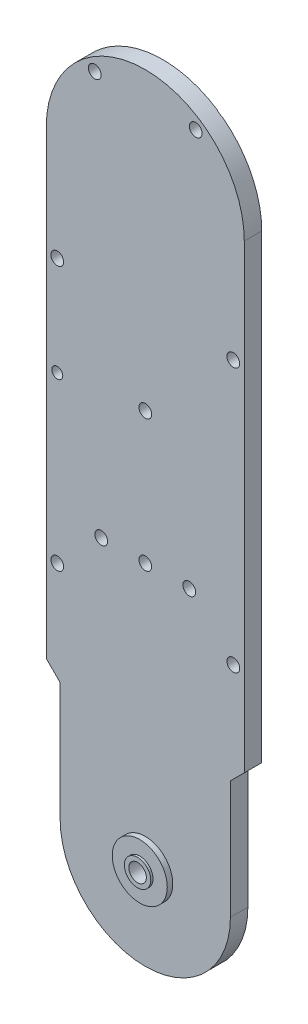
SolidWorks part; units mm, degrees
material "6061 Alloy"
ref_plane "Front Plane" through (0, 0, 0) normal (0, 0, 1) x (1, 0, 0)
ref_plane "Top Plane" through (0, 0, 0) normal (0, 1, 0) x (1, 0, 0)
ref_plane "Right Plane" through (0, 0, 0) normal (1, 0, 0) x (0, 0, -1)
sketch "Sketch1" plane through (0, 0, 0) normal (0, 0, 1) x (1, 0, 0)
  line L0 (-45, 0) -> (-45, -65.8631)
  line L1 (-45, -72.7369) -> (-45, -165.8631)
  line L2 (45, 0) -> (45, -65.8631)
  line L3 (45, -72.7369) -> (45, -165.8631)
  line L4 (-40, 0) -> (-40, -169.3) construction
  line L5 (40, 0) -> (40, -169.3) construction
  line L6 (45, -172.7369) -> (45, -165.8631)
  line L7 (45, -65.8631) -> (45, -72.7369)
  line L8 (-45, -165.8631) -> (-45, -172.7369)
  line L9 (-45, -65.8631) -> (-45, -72.7369)
  line L10 (-45, -172.7369) -> (-45, -219.3)
  line L11 (45, -172.7369) -> (45, -219.3)
  line L12 (45, -219.3) -> (38.7, -219.3)
  line L13 (-45, -219.3) -> (-38.7, -219.3)
  line L14 (-38.7, -219.3) -> (-38.7, -269.3)
  line L15 (38.7, -219.3) -> (38.7, -269.3)
  line L16 (0, 0) -> (0, -89.3) construction
  line L17 (0, -89.3) -> (0, -149.3) construction
  line L18 (-20, -149.3) -> (20, -149.3) construction
  line L19 (-45, -49.3) -> (-40, -49.3) construction
  line L20 (45, -49.3) -> (40, -49.3) construction
  circle A0 centre (0, 0) radius 60 construction
  circle A1 centre (0, 0) radius 45 construction
  circle A2 centre (0, 0) radius 40 construction
  arc A3 (-45, 0) -> (45, 0) centre (0, 0) cw
  arc A12 (-38.7, -269.3) -> (38.7, -269.3) centre (0, -269.3) ccw
  circle A17 centre (0, -269.3) radius 4
  circle A18 centre (0, -269.3) radius 38.2 construction
  circle A19 centre (0, -89.3) radius 2.5
  circle A20 centre (0, -149.3) radius 2.5
  circle A21 centre (20, -149.3) radius 2.5
  circle A22 centre (20, -149.3) radius 5 construction
  circle A25 centre (-20, -149.3) radius 2.5
  circle A26 centre (-20, -149.3) radius 5 construction
  circle A29 centre (-40, -49.3) radius 2.5
  circle A30 centre (-40, -169.3) radius 2.5
  circle A31 centre (40, -169.3) radius 2.5
  circle A32 centre (40, -49.3) radius 2.5
  arc A33 (0, 40) -> (-22.9431, 32.7661) centre (0, 0) ccw construction
  arc A34 (0, 40) -> (22.9431, 32.7661) centre (0, 0) cw construction
  circle A35 centre (-22.9431, 32.7661) radius 2.5
  circle A36 centre (22.9431, 32.7661) radius 2.5
  circle A38 centre (-40, -94.3) radius 2.5
  dimension "D1" = 120
  dimension "D2" = 90
  dimension "D3" = 80
  dimension "D4" = 5
  dimension "D5" = 49.3
  dimension "D6" = 120
  dimension "D7" = 38.7
  dimension "D8" = 8
  dimension "D9" = 20
  dimension "D10" = 10
  dimension "D11" = 45
  dimension "D12" = 120
extrude "Boss-Extrude1" add sketch "Sketch1" along normal blind 7.9375
sketch "Sketch3" plane through (0, 0, 7.9375) normal (0, 0, 1) x (1, 0, 0)
  circle A0 centre (0, -269.3) radius 4
  circle A1 centre (0, -269.3) radius 12.5
extrude "Boss-Extrude2" add sketch "Sketch3" along normal blind 5
sketch "Sketch4" plane through (0, 0, 12.9375) normal (0, 0, 1) x (1, 0, 0)
  circle A0 centre (0, -269.3) radius 6
  circle A1 centre (0, -269.3) radius 12.5
  dimension "D1" = 25
  dimension "D2" = 12
extrude "Cut-Extrude1" cut sketch "Sketch4" against normal blind 2.5
chamfer "Chamfer1" distance 10 angle 45 2 edges at (45, -219.3, 3.9688) (-45, -219.3, 3.9688)
sketch "Sketch5" plane through (0, 0, 12.9375) normal (0, 0, 1) x (1, 0, 0)
  circle A0 centre (0, -269.3) radius 6
extrude "Cut-Extrude2" cut sketch "Sketch5" against normal blind 1.5
hole_wizard "CSK for M5 Oval Head Machine Screw2" positions "3DSketch2" profile "Sketch7" countersink size "M5" standard "ANSI Metric" end condition through all
sketch3d "3DSketch2"
  line L0 (40, -49.3, 7.9375) -> (40, -49.3, 0) construction
  line L2 (0, -89.3, 7.9375) -> (0, -89.3, 0) construction
  line L4 (-40, -49.3, 7.9375) -> (-40, -49.3, 0) construction
  line L5 (-40, -169.3, 7.9375) -> (-40, -169.3, 0) construction
  line L6 (-20, -149.3, 7.9375) -> (-20, -149.3, 0) construction
  line L7 (0, -149.3, 7.9375) -> (0, -149.3, 0) construction
  line L8 (20, -149.3, 7.9375) -> (20, -149.3, 0) construction
  line L9 (40, -169.3, 7.9375) -> (40, -169.3, 0) construction
  point P0 (40, -49.3, 0)
  point P8 (0, -89.3, 0)
  point P16 (-40, -49.3, 0)
  point P20 (-40, -169.3, 0)
  point P24 (-20, -149.3, 0)
  point P28 (0, -149.3, 0)
  point P32 (20, -149.3, 0)
  point P36 (40, -169.3, 0)
sketch "Sketch7" plane through (40, -49.3, 0) normal (1, 0, 0) x (0, 1, 0)
  line L0 (0, 0) -> (0, 11.4375)
  line L1 (0, 11.4375) -> (2.9, 11.4375)
  line L2 (2.9, 11.4375) -> (2.9, 2.3)
  line L3 (2.9, 2.3) -> (5.2, 0)
  line L5 (5.2, 0) -> (0, 0)
  line L6 (-2.9, 2.3) -> (-5.2, 0) construction
  line L11 (0, -6.35) -> (0, 107.95) construction
  dimension "Thru Hole Dia." = 5.8
  dimension "Thru Hole Depth" = 11.4375
  dimension "Near C'Sink Dia." = 10.4
  dimension "Near C'Sink Angle" = 90
hole_wizard "CSK for M5 Oval Head Machine Screw3" positions "3DSketch3" profile "Sketch8" countersink size "M5" standard "ANSI Metric" end condition through all
sketch3d "3DSketch3"
  line L0 (22.9431, 32.7661, 7.9375) -> (22.9431, 32.7661, 0) construction
  line L1 (-22.9431, 32.7661, 7.9375) -> (-22.9431, 32.7661, 0) construction
  point P0 (22.9431, 32.7661, 0)
  point P4 (-22.9431, 32.7661, 0)
sketch "Sketch8" plane through (22.9431, 32.7661, 0) normal (1, 0, 0) x (0, 1, 0)
  line L0 (0, 0) -> (0, 11.4375)
  line L1 (0, 11.4375) -> (2.9, 11.4375)
  line L2 (2.9, 11.4375) -> (2.9, 2.3)
  line L3 (2.9, 2.3) -> (5.2, 0)
  line L5 (5.2, 0) -> (0, 0)
  line L6 (-2.9, 2.3) -> (-5.2, 0) construction
  line L11 (0, -6.35) -> (0, 107.95) construction
  dimension "Thru Hole Dia." = 5.8
  dimension "Thru Hole Depth" = 11.4375
  dimension "Near C'Sink Dia." = 10.4
  dimension "Near C'Sink Angle" = 90
